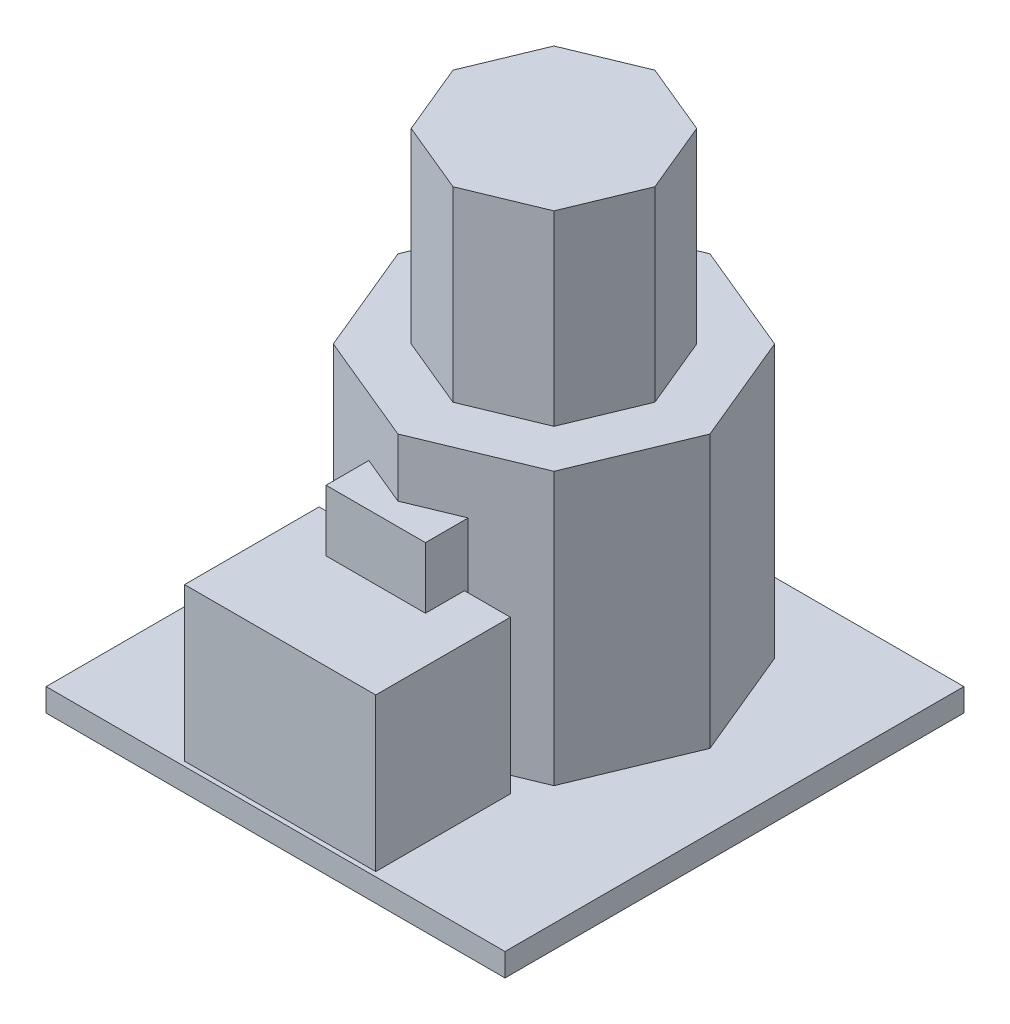
SolidWorks part; units mm, degrees
ref_plane "前视基准面" through (0, 0, 0) normal (0, 0, 1) x (1, 0, 0)
ref_plane "上视基准面" through (0, 0, 0) normal (0, 1, 0) x (1, 0, 0)
ref_plane "右视基准面" through (0, 0, 0) normal (1, 0, 0) x (0, 0, -1)
other "Configuration Table"
sketch "草图1" plane through (0, 0, 0) normal (0, 1, 0) x (1, 0, 0)
  line L1 (-150, -150) -> (150, -150)
  line L2 (-150, -150) -> (-150, 150)
  line L3 (-150, 150) -> (150, 150)
  line L4 (150, -150) -> (150, 150)
  line L5 (-150, -150) -> (150, 150) construction
  line L6 (-150, 150) -> (150, -150) construction
  point P0 (0, 0)
  dimension "D1" = 300
  dimension "D2" = 300
extrude "凸台-拉伸1" add sketch "草图1" against normal blind 15
sketch "草图2" plane through (0, 0, 0) normal (0, 1, 0) x (1, 0, 0)
  line L1 (102, 32) -> (72.1249, 104.1249)
  line L2 (72.1249, 104.1249) -> (0, 134)
  line L3 (0, 134) -> (-72.1249, 104.1249)
  line L4 (-72.1249, 104.1249) -> (-102, 32)
  line L5 (-102, 32) -> (-72.1249, -40.1249)
  line L6 (-72.1249, -40.1249) -> (0, -70)
  line L7 (0, -70) -> (72.1249, -40.1249)
  line L8 (72.1249, -40.1249) -> (102, 32)
  circle A0 centre (0, 32) radius 94.2357 construction
extrude "凸台-拉伸2" add sketch "草图2" along normal blind 178
sketch "草图3" plane through (0, 0, 0) normal (0, 1, 0) x (1, 0, 0)
  line L1 (66, 32) -> (46.669, 78.669)
  line L2 (46.669, 78.669) -> (0, 98)
  line L3 (0, 98) -> (-46.669, 78.669)
  line L4 (-46.669, 78.669) -> (-66, 32)
  line L5 (-66, 32) -> (-46.669, -14.669)
  line L6 (-46.669, -14.669) -> (0, -34)
  line L7 (0, -34) -> (46.669, -14.669)
  line L8 (46.669, -14.669) -> (66, 32)
  circle A0 centre (0, 32) radius 60.976 construction
extrude "凸台-拉伸3" add sketch "草图3" along normal blind 300
sketch "草图4" plane through (0, 0, 0) normal (0, 1, 0) x (1, 0, 0)
  line L1 (-62.5, -147) -> (62.5, -147)
  line L2 (-62.5, -147) -> (-62.5, -59)
  line L3 (-62.5, -59) -> (62.5, -59)
  line L4 (62.5, -147) -> (62.5, -59)
  line L5 (-62.5, -147) -> (62.5, -59) construction
  line L6 (-62.5, -59) -> (62.5, -147) construction
  point P0 (0, -103)
extrude "凸台-拉伸4" add sketch "草图4" along normal blind 100
sketch "草图5" plane through (0, 0, 0) normal (0, 1, 0) x (1, 0, 0)
  line L1 (-32.5, -84.5) -> (32.5, -84.5)
  line L2 (-32.5, -84.5) -> (-32.5, -39.5)
  line L3 (-32.5, -39.5) -> (32.5, -39.5)
  line L4 (32.5, -84.5) -> (32.5, -39.5)
  line L5 (-32.5, -84.5) -> (32.5, -39.5) construction
  line L6 (-32.5, -39.5) -> (32.5, -84.5) construction
  point P0 (0, -62)
extrude "凸台-拉伸5" add sketch "草图5" along normal blind 140
